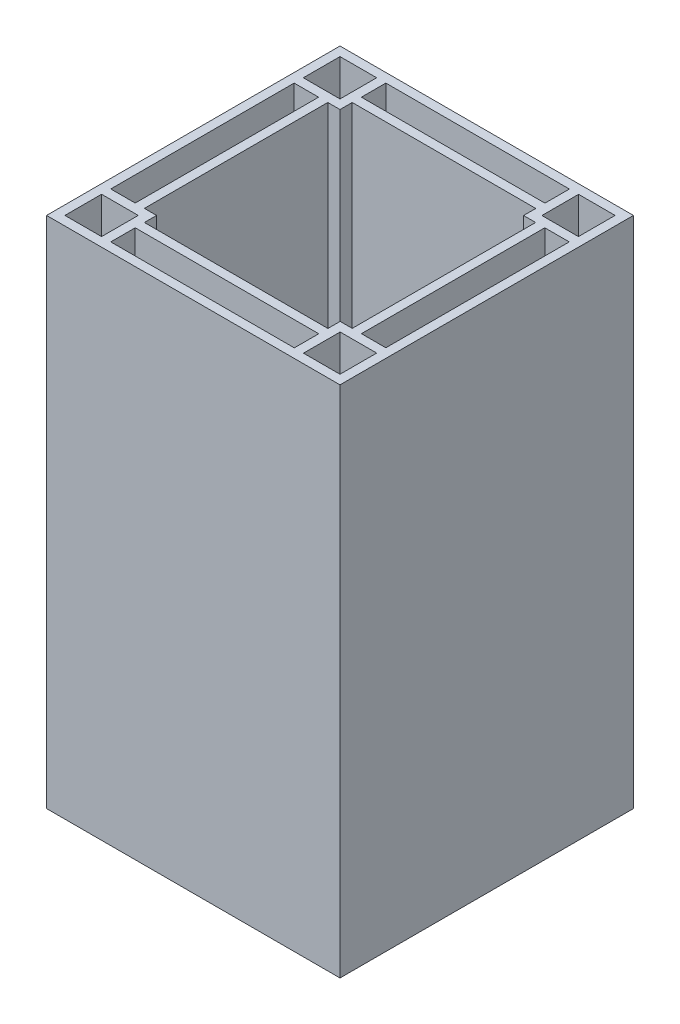
SolidWorks part; units mm, degrees
ref_plane "Front Plane" through (0, 0, 0) normal (0, 0, 1) x (1, 0, 0)
ref_plane "Top Plane" through (0, 0, 0) normal (0, 1, 0) x (1, 0, 0)
ref_plane "Right Plane" through (0, 0, 0) normal (1, 0, 0) x (0, 0, -1)
sketch "Sketch1" plane through (0, 0, 0) normal (1, 0, 0) x (0, 0, -1)
  line L1 (-50.8, -101.6) -> (50.8, -101.6)
  line L2 (-50.8, -101.6) -> (-50.8, 101.6)
  line L3 (-50.8, 101.6) -> (50.8, 101.6)
  line L4 (50.8, -101.6) -> (50.8, 101.6)
  line L5 (-50.8, -101.6) -> (50.8, 101.6) construction
  line L6 (-50.8, 101.6) -> (50.8, -101.6) construction
  point P0 (0, 0)
extrude "Boss-Extrude1" add sketch "Sketch1" along normal blind 101.6
sketch "Sketch2" plane through (0, 101.6, 0) normal (0, 1, 0) x (1, 0, 0)
  line L0 (101.6, 50.8) -> (0, 50.8) construction
  line L1 (3.175, 47.625) -> (15.875, 47.625)
  line L2 (3.175, 47.625) -> (3.175, 34.925)
  line L3 (3.175, 34.925) -> (15.875, 34.925)
  line L4 (15.875, 47.625) -> (15.875, 34.925)
  line L5 (0, 50.8) -> (0, -50.8) construction
  line L6 (101.6, -50.8) -> (0, -50.8) construction
  line L7 (3.175, -34.925) -> (15.875, -34.925)
  line L8 (3.175, -34.925) -> (3.175, -47.625)
  line L9 (3.175, -47.625) -> (15.875, -47.625)
  line L10 (15.875, -34.925) -> (15.875, -47.625)
  line L11 (101.6, 50.8) -> (101.6, -50.8) construction
  line L12 (85.7769, -34.925) -> (98.425, -34.925)
  line L13 (85.7769, -34.925) -> (85.7769, -47.625)
  line L14 (85.7769, -47.625) -> (98.425, -47.625)
  line L15 (98.425, -34.925) -> (98.425, -47.625)
  line L17 (98.425, 47.625) -> (85.7769, 47.625)
  line L18 (98.425, 47.625) -> (98.425, 34.925)
  line L19 (98.425, 34.925) -> (85.7769, 34.925)
  line L20 (85.7769, 47.625) -> (85.7769, 34.925)
  dimension "D1" = 3.175
  dimension "D2" = 3.175
  dimension "D3" = 12.7
  dimension "D4" = 12.7
  dimension "D5" = 3.175
  dimension "D6" = 3.175
  dimension "D7" = 12.7
  dimension "D8" = 12.7
  dimension "D9" = 3.175
extrude "Cut-Extrude1" cut sketch "Sketch2" against normal blind 203.2
sketch "Sketch3" plane through (0, 101.6, 0) normal (0, 1, 0) x (1, 0, 0)
  line L0 (0, 50.8) -> (0, -50.8) construction
  line L1 (3.175, -31.75) -> (11.6408, -31.75)
  line L2 (3.175, -31.75) -> (3.175, 31.75)
  line L3 (3.175, 31.75) -> (11.6408, 31.75)
  line L4 (11.6408, -31.75) -> (11.6408, 31.75)
  line L5 (19.05, 47.625) -> (82.6019, 47.625)
  line L6 (19.05, 47.625) -> (19.05, 39.1592)
  line L7 (19.05, 39.1592) -> (82.6019, 39.1592)
  line L8 (82.6019, 47.625) -> (82.6019, 39.1592)
  line L9 (101.6, 50.8) -> (0, 50.8) construction
  line L10 (15.875, -34.925) -> (3.175, -34.925) construction
  line L11 (3.175, 34.925) -> (15.875, 34.925) construction
  line L12 (15.875, 34.925) -> (15.875, 47.625) construction
  line L13 (85.7769, 47.625) -> (85.7769, 34.925) construction
  line L14 (101.6, 50.8) -> (101.6, -50.8) construction
  line L15 (98.425, 31.75) -> (89.9584, 31.75)
  line L16 (98.425, 31.75) -> (98.425, -31.75)
  line L17 (98.425, -31.75) -> (89.9584, -31.75)
  line L18 (89.9584, 31.75) -> (89.9584, -31.75)
  line L19 (19.05, -39.1592) -> (82.6019, -39.1592)
  line L20 (19.05, -39.1592) -> (19.05, -47.625)
  line L21 (19.05, -47.625) -> (82.6019, -47.625)
  line L22 (82.6019, -39.1592) -> (82.6019, -47.625)
  line L23 (101.6, -50.8) -> (0, -50.8) construction
  line L25 (19.05, 35.9842) -> (82.6019, 35.9842)
  line L26 (19.05, 35.9842) -> (19.05, -35.9842)
  line L27 (19.05, -35.9842) -> (82.6019, -35.9842)
  line L28 (82.6019, 35.9842) -> (82.6019, -35.9842)
  line L29 (14.8158, 31.75) -> (86.7834, 31.75)
  line L30 (14.8158, 31.75) -> (14.8158, -31.75)
  line L31 (14.8158, -31.75) -> (86.7834, -31.75)
  line L32 (86.7834, 31.75) -> (86.7834, -31.75)
  dimension "D1" = 3.175
  dimension "D2" = 3.175
  dimension "D3" = 3.175
  dimension "D4" = 3.175
  dimension "D5" = 3.175
  dimension "D6" = 3.175
  dimension "D7" = 8.4658
  dimension "D8" = 8.4658
  dimension ".3333" = 8.4658
  dimension "D9" = 8.4666
  dimension "D10" = 3.175
  dimension "D11" = 3.175
  dimension "D12" = 3.175
  dimension "D13" = 3.175
  dimension "D14" = 3.175
  dimension ".125" = 3.175
extrude "Cut-Extrude2" cut sketch "Sketch3" against normal blind 200.025 contours L30 L31 L26 L29 | L26 L31 L28 L29 | L26 L29 L28 L25 | L32 L29 L28 L31 | L15 L18 L17 L16 | L8 L5 L6 L7 | L1 L4 L3 L2 | L22 L19 L20 L21 | L31 L26 L27 L28 region at (7.4079, 101.6, 0) region at (50.826, 101.6, -43.3921) region at (94.1917, 101.6, 0) region at (50.826, 101.6, 43.3921) region at (50.826, 101.6, -33.8671) region at (50.826, 101.6, 0) region at (16.9329, 101.6, 0) region at (84.6927, 101.6, 0) region at (50.826, 101.6, 33.8671)
sketch "Sketch4" plane through (101.6, 0, 0) normal (1, 0, 0) x (0, 0, -1)
  line L0 (50.8, -101.6) -> (50.8, 101.6) construction
  line L1 (-50.8, 101.6) -> (50.8, 101.6)
  line L2 (-50.8, 101.6) -> (-50.8, 76.258)
  line L3 (-50.8, 76.258) -> (50.8, 76.258)
  line L4 (50.8, 101.6) -> (50.8, 76.258)
extrude "Cut-Extrude3" cut sketch "Sketch4" against normal blind 101.6
hole_wizard "1/2-13 Tapped Hole2" positions "3DSketch1" profile "Sketch6" tap size "1/2-13" standard "ANSI Inch" end condition through all
sketch3d "3DSketch1"
  line L0 (14.8158, -98.425, 0) -> (88.5333, -98.425, 0) construction
  line L1 (14.8158, -98.425, -31.75) -> (14.8158, -98.425, 31.75) construction
  line L2 (50.826, -98.425, 35.9842) -> (50.826, -98.425, -41.058) construction
  line L3 (19.05, -98.425, 35.9842) -> (82.6019, -98.425, 35.9842) construction
  point P0 (50.826, -98.425, 0)
  dimension "D1" = 0
  dimension "D2" = 0
sketch "Sketch6" plane through (50.826, -98.425, 0) normal (1, 0, 0) x (0, 0, 1)
  line L0 (0, 0) -> (0, 3.175)
  line L1 (0, 3.175) -> (5.3581, 3.175)
  line L2 (5.3581, 3.175) -> (5.3581, 0)
  line L5 (5.3581, 0) -> (0, 0)
  line L11 (0, -6.35) -> (0, 107.95) construction
  dimension "Thru Tap Drill Dia." = 10.7163
  dimension "Thru Tap Drill Depth" = 3.175
cosmetic thread "Hole Thread1" parameters "D2"=12.7
